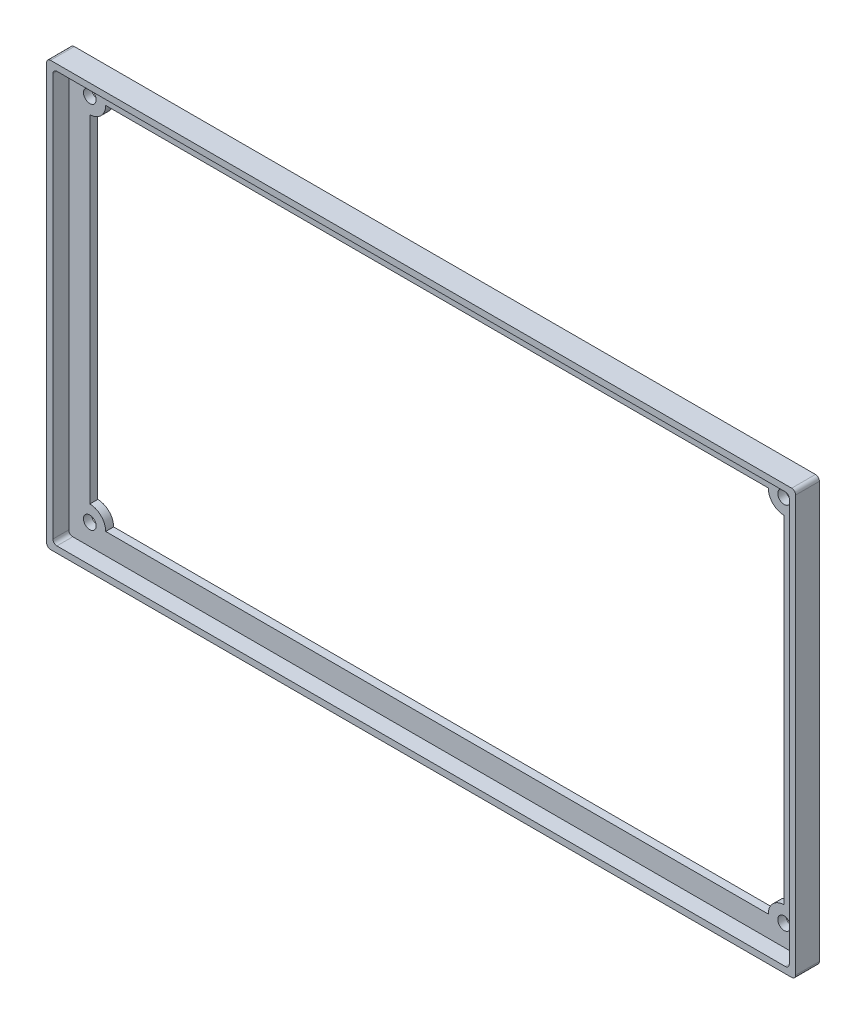
SolidWorks part; units mm, degrees
ref_plane "Спереди" through (0, 0, 0) normal (0, 0, 1) x (1, 0, 0)
ref_plane "Сверху" through (0, 0, 0) normal (0, 1, 0) x (1, 0, 0)
ref_plane "Справа" through (0, 0, 0) normal (1, 0, 0) x (0, 0, -1)
sketch "Эскиз1" plane through (0, 0, 0) normal (0, 0, 1) x (1, 0, 0)
  line L0 (181.9, 95.9) -> (181.9, 10.9)
  line L1 (0, 0) -> (188.8, 0)
  line L2 (0, 0) -> (0, 106.8)
  line L3 (0, 106.8) -> (188.8, 106.8)
  line L4 (188.8, 0) -> (188.8, 106.8)
  line L5 (1.6, 1.6) -> (187.2, 1.6)
  line L6 (1.6, 1.6) -> (1.6, 105.2)
  line L7 (1.6, 105.2) -> (187.2, 105.2)
  line L8 (187.2, 1.6) -> (187.2, 105.2)
  line L13 (6.9, 6.9) -> (181.9, 6.9) construction
  line L14 (6.9, 6.9) -> (6.9, 99.9) construction
  line L15 (6.9, 99.9) -> (181.9, 99.9) construction
  line L16 (181.9, 6.9) -> (181.9, 99.9) construction
  line L17 (177.9, 6.9) -> (10.9, 6.9)
  line L18 (6.9, 10.9) -> (6.9, 95.9)
  line L19 (10.9, 99.9) -> (177.9, 99.9)
  circle A0 centre (6.9, 99.9) radius 1.6
  circle A1 centre (181.9, 99.9) radius 1.6
  circle A2 centre (181.9, 6.9) radius 1.6
  circle A3 centre (6.9, 6.9) radius 1.6
  circle A4 centre (181.9, 6.9) radius 4
  circle A5 centre (6.9, 6.9) radius 4
  circle A6 centre (6.9, 99.9) radius 4
  circle A7 centre (181.9, 99.9) radius 4
  dimension "D9" = 3.2
  dimension "D10" = 3.2
  dimension "D13" = 3.2
  dimension "D15" = 3.2
  dimension "D16" = 8
  dimension "D17" = 8
  dimension "D18" = 8
  dimension "D19" = 8
  dimension "D2" = 5.3
  dimension "D3" = 1.6
  dimension "D4" = 1.6
  dimension "D5" = 5.3
  dimension "D6" = 93
  dimension "D7" = 1.6
  dimension "D8" = 5.3
  dimension "D11" = 5.3
  dimension "D12" = 1.6
  dimension "D14" = 175
extrude "Бобышка-Вытянуть1" add sketch "Эскиз1" along normal blind 2 contours L5 L8 L7 L6 A7 L0 A4 L17 A5 L18 A6 L19 | A6 A0 | A7 A1 | A4 A2 | A5 A3 region at (179.1516, 97.1516, 0) region at (184.6484, 9.6484, 0) region at (9.6484, 97.1516, 0) region at (4.1516, 4.1516, 0) region at (3.7256, 53.4, 0)
extrude "Бобышка-Вытянуть2" add sketch "Эскиз1<3>" along normal blind 6 contours L1 L4 L3 L2 L8 L5 L6 L7 region at (0.2169, 53.4, 0)
sketch "Эскиз1<3>" plane through (0, 0, 0) normal (0, 0, 1) x (1, 0, 0) same geometry as "Эскиз1"
fillet "Скругление1" radius 1 8 edges at (0, 0, 3) (188.8, 0, 3) (188.8, 106.8, 3) (0, 106.8, 3) (1.6, 105.2, 4) (1.6, 1.6, 4) (187.2, 1.6, 4) (187.2, 105.2, 4)
